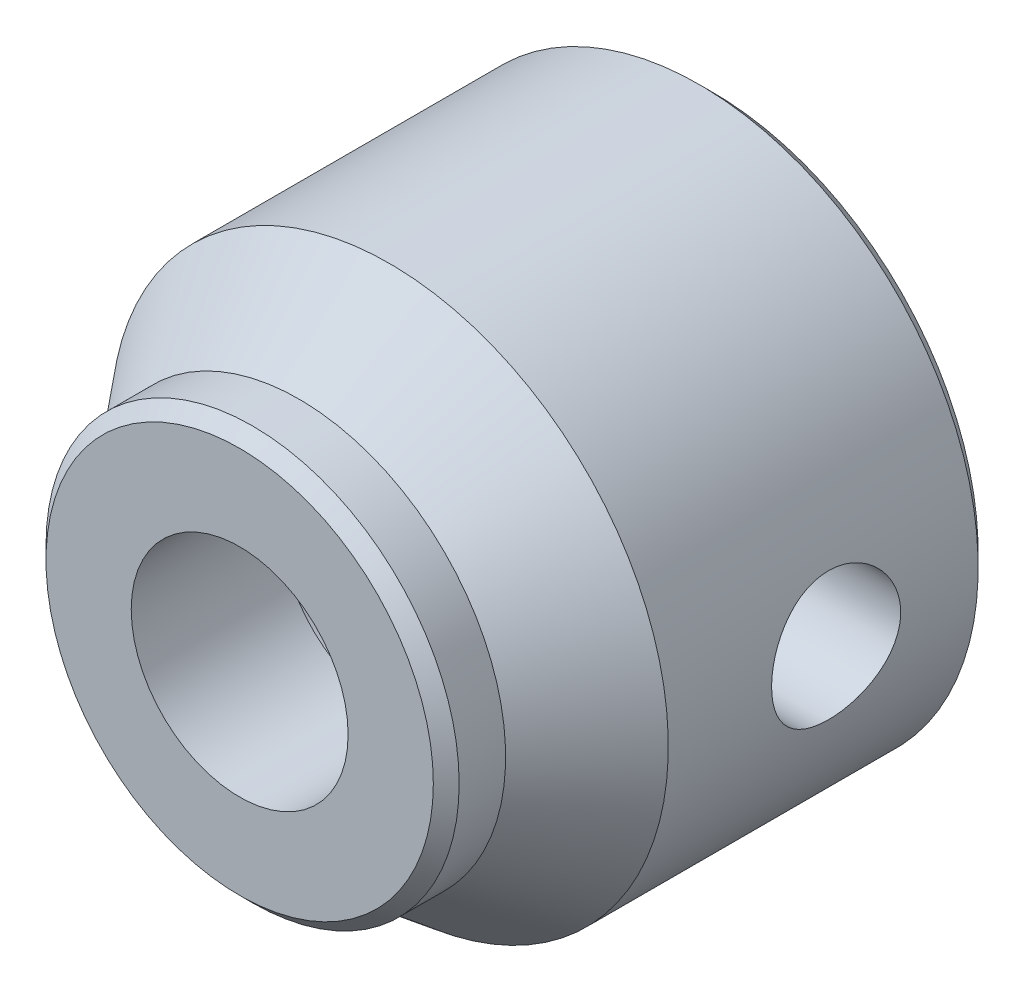
SolidWorks part; units mm, degrees
ref_plane "Top" through (0, 0, 0) normal (0, 0, 1) x (1, 0, 0)
ref_plane "Front" through (0, 0, 0) normal (0, 1, 0) x (1, 0, 0)
ref_plane "Right" through (0, 0, 0) normal (1, 0, 0) x (0, 0, -1)
ref_plane "Base Tangent Plane" through (5.4, 0, 0) normal (1, 0, 0) x (0, 0, -1)
sketch "Body Sketch" plane through (0, 0, 0) normal (0, 1, 0) x (-1, 0, 0)
  line L1 (1, 9.15) -> (4, 9.15)
  line L2 (4, 9.15) -> (4, 8)
  line L3 (4, 8) -> (5.4, 6.25)
  line L4 (5.4, 6.25) -> (5.4, 0)
  line L5 (5.4, 0) -> (2.5, 0)
  line L8 (0, 0) -> (0, 9.15) construction
  line L9 (1, 9.15) -> (1, 6.25)
  line L10 (1, 6.25) -> (2.5, 6.25)
  line L11 (2.5, 6.25) -> (2.5, 0)
  point P5 (0, 0)
  dimension "D4" = 5.4
  dimension "D5" = 2.5
  dimension "D7" = 1
  dimension "D8" = 6.25
  dimension "D2" = 2.9
  dimension "D6" = 1.75
  dimension "D3" = 4
  dimension "D9" = 1.5
revolve "Body Revolve" add sketch "Body Sketch" angle 360 about L8
hole_wizard "Connector M5x0.8 Tapped Hole" positions "Connector Position Sketch" profile "Sketch5" tap size "M5x0.8" standard "ANSI Metric"
sketch "Connector Position Sketch" plane through (0, 0, 9.15) normal (0, 0, 1) x (1, 0, 0)
  point P0 (0, 0)
cosmetic thread "Connector Hole Thread" parameters "D1"=5, "D2"=5
sketch "Sketch5" plane through (0, 0, 9.15) normal (1, 0, 0) x (0, -1, 0)
  line L0 (0, 0) -> (0, 8.6618)
  line L1 (0, 8.6618) -> (2.1, 7.4)
  line L2 (2.1, 7.4) -> (2.1, 0)
  line L5 (2.1, 0) -> (0, 0)
  line L10 (0, 8.6618) -> (-2.1, 7.4) construction
  line L11 (0, -6.35) -> (0, 107.95) construction
  dimension "Tap Drill Dia." = 4.2
  dimension "Tap Drill Depth" = 7.4
  dimension "Drill Angle" = 118
hole_wizard "Set Screw M3x0.5 Tapped Hole" positions "Set Screw Position Sketch" profile "Set Screw Profile Sketch" tap size "M3x0.5" standard "ANSI Metric" end condition up to next
sketch3d "Set Screw Position Sketch"
  point P0 (5.4, 0, 3)
  dimension "D1" = 3
sketch "Set Screw Profile Sketch" plane through (5.4, 0, 3) normal (0, 1, 0) x (0, 0, -1)
  line L0 (0, 0) -> (0, 2.9)
  line L1 (0, 2.9) -> (1.25, 2.9)
  line L2 (1.25, 2.9) -> (1.25, 0)
  line L5 (1.25, 0) -> (0, 0)
  line L11 (0, -6.35) -> (0, 107.95) construction
  dimension "Thru Tap Drill Dia." = 2.5
  dimension "Thru Tap Drill Depth" = 2.9
cosmetic thread "Set Screw 1 Hole Thread" parameters "D2"=3
chamfer "Edge Chamfers" distance 0.25 angle 45 2 edges at (-5.4, 0, 0) (-4, 0, 9.15)
equation "\"Base Diameter\"= 10.8"
equation "\"D4@Body Sketch\"=\"Base Diameter\"/2"
equation "\"D1@Base Tangent Plane\"=\"Base Diameter\"/2"
